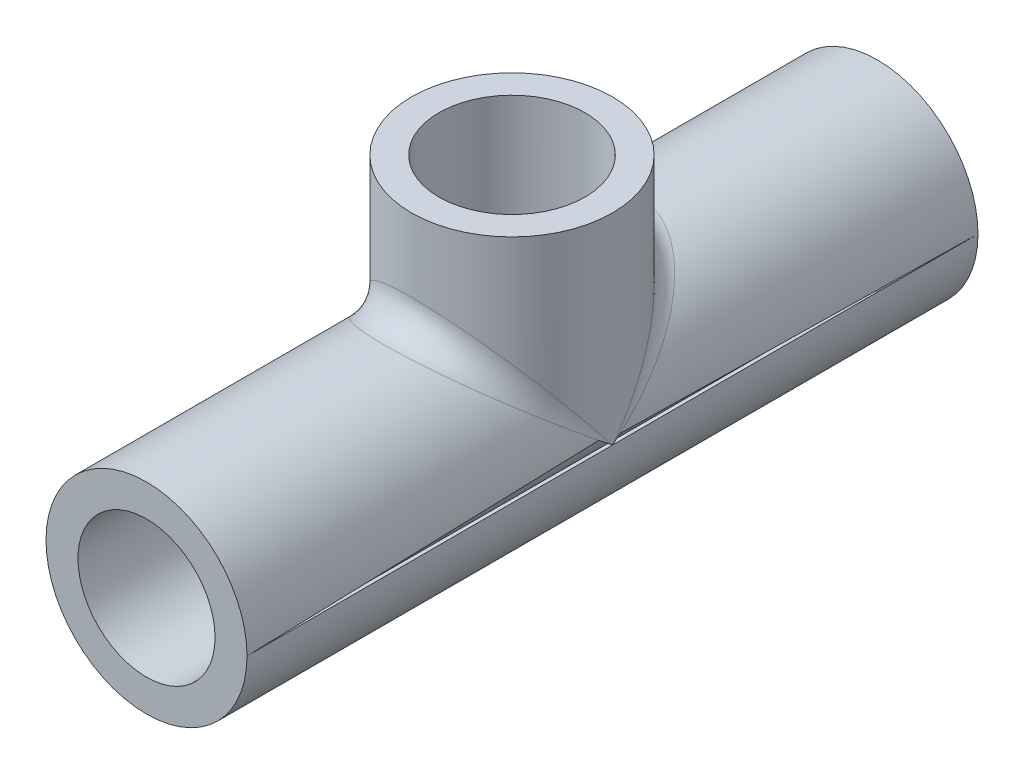
SolidWorks part; units mm, degrees
material "Nylon 101"
ref_plane "Front" through (0, 0, 0) normal (0, 0, 1) x (1, 0, 0)
ref_plane "Top" through (0, 0, 0) normal (0, 1, 0) x (1, 0, 0)
ref_plane "Right" through (0, 0, 0) normal (1, 0, 0) x (0, 0, -1)
ref_axis "Axis1" through (0, 0, 55) along (0, 0, -1)
sketch "Sketch1" plane through (0, 0, 0) normal (0, 0, 1) x (1, 0, 0)
  circle A0 centre (0, 0) radius 11
  circle A1 centre (0, 0) radius 7.5
  dimension "D1" = 22
  dimension "D2" = 15
extrude "Boss-Extrude1" add sketch "Sketch1" along normal blind 80
sketch "Sketch2" plane through (0, 0, 0) normal (0, 1, 0) x (1, 0, 0)
  line L0 (0, 0) -> (0, -80) construction
  line L1 (7.5, 0) -> (-7.5, 0) construction
  line L2 (-11, -80) -> (11, -80) construction
  circle A0 centre (0, -40) radius 8
  circle A1 centre (0, -40) radius 11
  dimension "D1" = 16
  dimension "D2" = 22
extrude "Boss-Extrude2" add sketch "Sketch2" along normal blind 2 and the other way up to surface from offset 20 other way up to face at (11, 0, 80)
sketch "Sketch3" plane through (0, 22, 0) normal (0, 1, 0) x (1, 0, 0)
  circle A0 centre (0, -40) radius 8 construction
  circle A1 centre (0, -40) radius 8
extrude "Cut-Extrude1" cut sketch "Sketch3" against normal blind 16
fillet "Fillet1" radius 10 2 edges at (4.5, 6, 40) (-4.5, 6, 40)
fillet "Fillet2" radius 3 2 edges at (0, 11, 29) (0, 11, 51)
